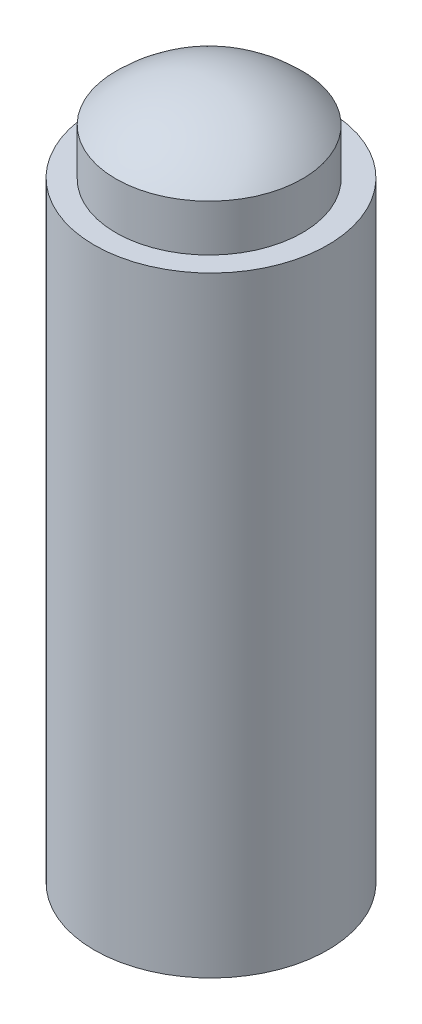
SolidWorks part; units mm, degrees
ref_plane "Front Plane" through (0, 0, 0) normal (0, 0, 1) x (1, 0, 0)
ref_plane "Top Plane" through (0, 0, 0) normal (0, 1, 0) x (1, 0, 0)
ref_plane "Right Plane" through (0, 0, 0) normal (1, 0, 0) x (0, 0, -1)
sketch "Sketch1" plane through (0, 0, 0) normal (0, 1, 0) x (1, 0, 0)
  circle A0 centre (0, 0) radius 3
  dimension "D1" = 6
extrude "Boss-Extrude1" add sketch "Sketch1" along normal blind 15.7
sketch "Sketch2" plane through (0, 0, 0) normal (0, -1, 0) x (1, 0, 0)
  circle A0 centre (0, 0) radius 1.25
  dimension "D1" = 2.5
extrude "Cut-Extrude1" cut sketch "Sketch2" against normal blind 0.5
sketch "Sketch4" plane through (0, 15.7, 0) normal (0, 1, 0) x (1, 0, 0)
  circle A0 centre (0, -0.0477) radius 2.4
  dimension "D1" = 4.8
extrude "Boss-Extrude2" add sketch "Sketch4" along normal blind 1.2
dome "Dome1" faces to dome 1 distance 1 reverse direction no elliptical dome no face at (0, 16.9, 2.4477) parameters "D1"=1
